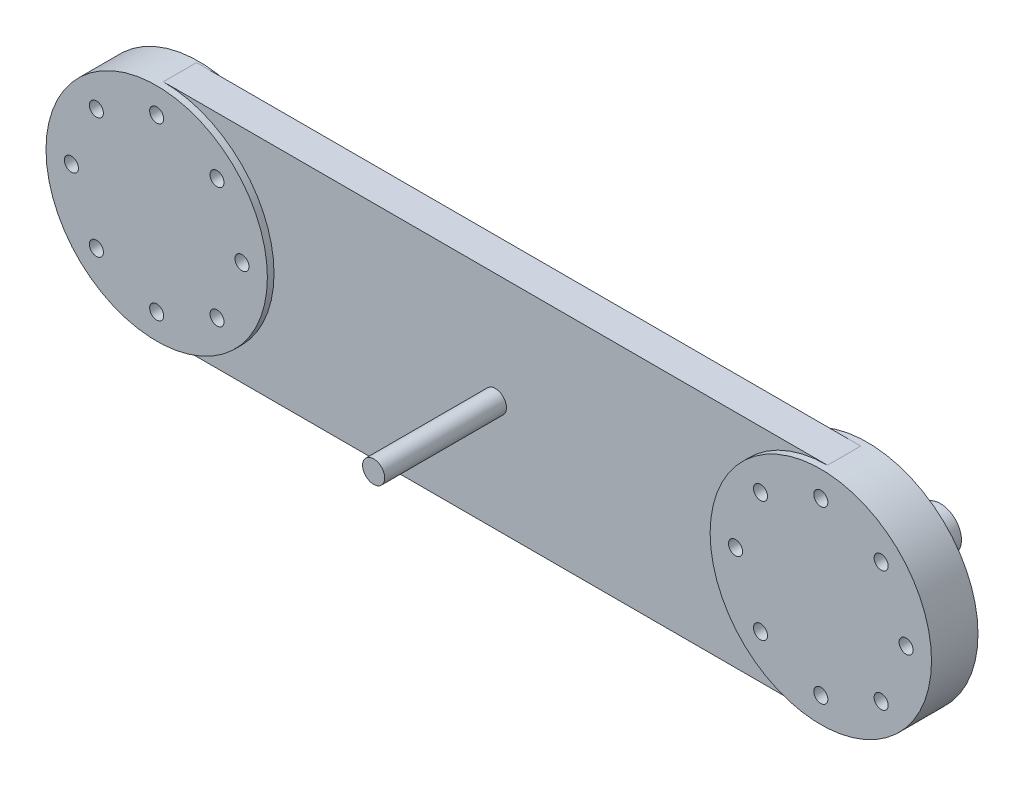
SolidWorks part; units mm, degrees
note: The reader was unsure of these and kept them because the rebuilt part matched: shared geometry of "草图1<28>", "草图1<30>", "草图1<31>", "草图1<32>", "草图1<35>", "草图1<36>", "草图1<37>", "草图1<41>", "草图1<43>".
material "3003 Alloy"
ref_plane "前视基准面" through (0, 0, 0) normal (0, 0, 1) x (1, 0, 0)
ref_plane "上视基准面" through (0, 0, 0) normal (0, 1, 0) x (1, 0, 0)
ref_plane "右视基准面" through (0, 0, 0) normal (1, 0, 0) x (0, 0, -1)
sketch "草图1" plane through (0, 0, 0) normal (0, 0, 1) x (1, 0, 0)
  line L0 (0, 100) -> (-300, 0) construction
  line L5 (0, 0) -> (-300, 0)
  line L6 (0, 0) -> (0, 100)
  line L7 (0, 100) -> (-300, 100)
  line L8 (-300, 0) -> (-300, 100)
  line L9 (-300, 100) -> (0, 0) construction
  line L10 (-300, 50) -> (-250, 50)
  line L11 (-250, 50) -> (-300, 100) construction
  line L12 (-300, 50) -> (-264.6447, 85.3553) construction
  line L13 (-300, 50) -> (-335.3553, 14.6447)
  line L14 (-150, 50) -> (-150, 0)
  line L15 (-264.6447, 85.3553) -> (-335.3553, 85.3553) construction
  line L16 (-264.6447, 85.3553) -> (-264.6447, 14.6447) construction
  line L17 (-264.6447, 14.6447) -> (-335.3553, 14.6447) construction
  line L18 (-335.3553, 85.3553) -> (-335.3553, 14.6447) construction
  line L19 (-150, 0) -> (-150, 100) construction
  line L20 (6.25, 50) -> (8.25, 50)
  line L21 (6.25, 50) -> (8.25, 50)
  line L22 (6.25, 47.9959) -> (6.25, 52.0041)
  line L23 (8.25, 47.9959) -> (8.25, 52.0041)
  line L24 (6.25, 52.0041) -> (8.25, 52.0041)
  line L25 (6.25, 52.0041) -> (5.92, 52.0041)
  line L26 (6.25, 52.0041) -> (6.25, 50)
  line L27 (6.25, 52.0041) -> (6.25, 47.9959)
  line L28 (6.25, 52.0041) -> (5.137, 52.0041)
  line L29 (6.25, 50) -> (5.137, 50)
  line L30 (5.137, 52.0041) -> (5.137, 47.9959)
  line L31 (6.25, 47.9959) -> (5.137, 47.9959)
  line L32 (6.25, 47.9959) -> (8.25, 47.9959)
  circle A6 centre (0, 50) radius 50
  circle A7 centre (0, 50) radius 25
  circle A8 centre (-300, 50) radius 50
  circle A9 centre (-300, 50) radius 25
  circle A12 centre (-150, 50) radius 5
  circle A14 centre (-261.4697, 50) radius 3.175
  circle A23 centre (-38.5303, 50) radius 3.175
  circle A30 centre (-272.7549, 22.7549) radius 3.175
  circle A31 centre (-300, 11.4697) radius 3.175
  circle A32 centre (-327.2451, 22.7549) radius 3.175
  circle A33 centre (-338.5303, 50) radius 3.175
  circle A34 centre (-327.2451, 77.2451) radius 3.175
  circle A35 centre (-300, 88.5303) radius 3.175
  circle A36 centre (-272.7549, 77.2451) radius 3.175
  circle A37 centre (-27.2451, 77.2451) radius 3.175
  circle A38 centre (-27.2451, 77.2451) radius 3.175
  circle A39 centre (0, 88.5303) radius 3.175
  circle A40 centre (27.2451, 77.2451) radius 3.175
  circle A41 centre (38.5303, 50) radius 3.175
  circle A42 centre (27.2451, 22.7549) radius 3.175
  circle A43 centre (0, 11.4697) radius 3.175
  circle A44 centre (-27.2451, 22.7549) radius 3.175
  circle A45 centre (0, 50) radius 6.25
  circle A46 centre (0, 50) radius 9.525
  point P70 (-300, 50)
  point P87 (0, 50)
  dimension "D1" = 100
  dimension "D2" = 300
  dimension "D3" = 50
  dimension "D4" = 50
  dimension "D5" = 10
  dimension "D6" = 2
  dimension "D7" = 6.35
  dimension "D8" = 12.5
  dimension "D9" = 19.05
extrude "凸台-拉伸18" add sketch "草图1" along normal blind 13 contours A8 | A6
extrude "凸台-拉伸21" add sketch "草图1<28>" along normal blind 15 contours L5 L8 L7 L6
sketch "草图1<28>" plane through (0, 0, 0) normal (0, 0, 1) x (1, 0, 0) same geometry as "草图1"
extrude "凸台-拉伸22" add sketch "草图1<30>" along normal blind 70 contours A12
sketch "草图1<30>" plane through (0, 0, 0) normal (0, 0, 1) x (1, 0, 0) same geometry as "草图1"
extrude "切除-拉伸2" cut sketch "草图1<31>" along normal blind 41 contours A8
sketch "草图1<31>" plane through (0, 0, 0) normal (0, 0, 1) x (1, 0, 0) same geometry as "草图1"
extrude "凸台-拉伸23" add sketch "草图1<32>" along normal blind 18 and the other way blind 1 contours A8
sketch "草图1<32>" plane through (0, 0, 0) normal (0, 0, 1) x (1, 0, 0) same geometry as "草图1"
extrude "切除-拉伸5" cut sketch "草图1<35>" against normal blind 69 and the other way blind 130
sketch "草图1<35>" plane through (0, 0, 0) normal (0, 0, 1) x (1, 0, 0) same geometry as "草图1"
extrude "切除-拉伸6" cut sketch "草图1<36>" along normal blind 34 contours A6
sketch "草图1<36>" plane through (0, 0, 0) normal (0, 0, 1) x (1, 0, 0) same geometry as "草图1"
extrude "凸台-拉伸24" add sketch "草图1<37>" against normal blind 3 and the other way blind 18 contours A6
sketch "草图1<37>" plane through (0, 0, 0) normal (0, 0, 1) x (1, 0, 0) same geometry as "草图1"
extrude "切除-拉伸7" cut sketch "草图1<41>" along normal blind 87 and the other way blind 98 contours A36 | L8 A35 | L8 A35 | A34 | A33 | L13 A32 | L8 A31 | A30 | L10 A14 | L10 A14 | A44 | A23 | A37 | A39 L6 | A39 L6 | A40 | A42 | A41 | A43 L6 | A43 L6
sketch "草图1<41>" plane through (0, 0, 0) normal (0, 0, 1) x (1, 0, 0) same geometry as "草图1"
sketch "Sketch1" plane through (0, 0, -3) normal (0, 0, -1) x (-1, 0, 0)
  line L0 (-50, 50) -> (50, 50) construction
  line L1 (0, 0) -> (0, 100) construction
  circle A0 centre (0, 50) radius 50 construction
  arc A1 (0, 0) -> (0, 100) centre (0, 50) ccw construction
  point P11 (0, 50)
ref_point "RotatioanAxixCentre"
sketch "Sketch2" plane through (0, 100, 0) normal (0, 1, 0) x (1, 0, 0)
  line L0 (0, -18) -> (0, 3)
  line L2 (50, 3) -> (-50, 3) construction
  point P3 (0, -7.5)
  dimension "D1" = 10.5
extrude "the extended shaft connecter" add sketch "草图1<43>" against normal blind 36 contours L6 A46 A45 L25 L24 L23 L32 L31 | L6 A46 A45
sketch "草图1<43>" plane through (0, 0, 0) normal (0, 0, 1) x (1, 0, 0) same geometry as "草图1"
ref_plane "基准面1" through (5.92, 52.0041, -36) normal (-0.3207, 0.9472, 0) x (0.9472, 0.3207, 0)
sketch "草图3" plane through (0, 0, 0) normal (1, 0, 0) x (0, 0, -1)
  line L0 (27, 50) -> (27, 59.525)
  line L1 (36, 59.525) -> (3, 59.525) construction
  line L2 (27, 59.525) -> (32, 59.525)
  line L3 (32, 59.525) -> (32, 50)
  circle A0 centre (32, 50) radius 1.0922
  circle A1 centre (27, 50) radius 1.0922
  point P4 (0, 0)
  point P6 (0, 0)
  point P7 (0, 0)
  point P8 (0, 0)
  point P9 (0, 0)
  point P14 (0, 0)
  dimension "D1" = 2.1844
  dimension "D2" = 2.1844
extrude "切除-拉伸8" cut sketch "草图3" against normal blind 31
sketch "草图5" plane through (0, 0, 0) normal (0, 1, 0) x (1, 0, 0)
  circle A0 centre (0, 32) radius 1.0922
  circle A1 centre (0, 27) radius 1.0922
  point P4 (0, 0)
  point P5 (0, 0)
  point P6 (0, 0)
  point P7 (0, 0)
  dimension "D1" = 2.1844
  dimension "D2" = 2.1844
extrude "screw_holes2" cut sketch "草图5" along normal up to vertex
